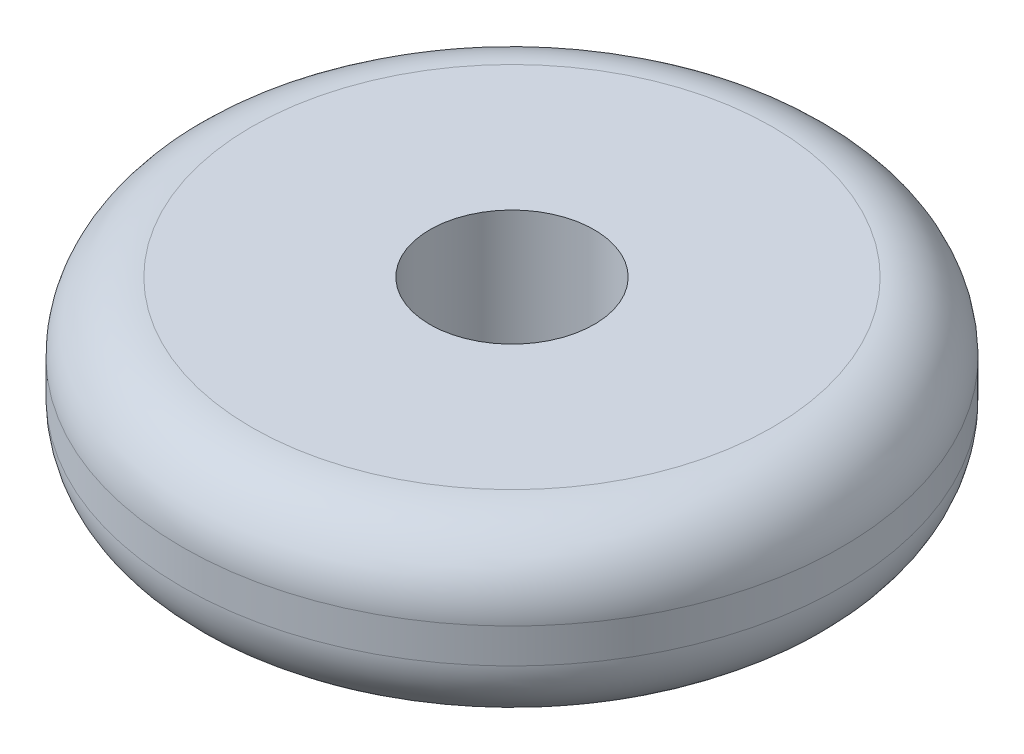
SolidWorks part; units mm, degrees
ref_plane "Front Plane" through (0, 0, 0) normal (0, 0, 1) x (1, 0, 0)
ref_plane "Top Plane" through (0, 0, 0) normal (0, 1, 0) x (1, 0, 0)
ref_plane "Right Plane" through (0, 0, 0) normal (1, 0, 0) x (0, 0, -1)
sketch "Sketch1" plane through (0, 0, 0) normal (0, 1, 0) x (1, 0, 0)
  circle A0 centre (0, 0) radius 19.05
  circle A1 centre (0, 0) radius 4.75
  dimension "D1" = 38.1
  dimension "D2" = 9.5
extrude "Boss-Extrude1" add sketch "Sketch1" along normal blind 10
fillet "Fillet1" radius 4 2 edges at (0, 0, 19.05) (0, 10, 19.05)
